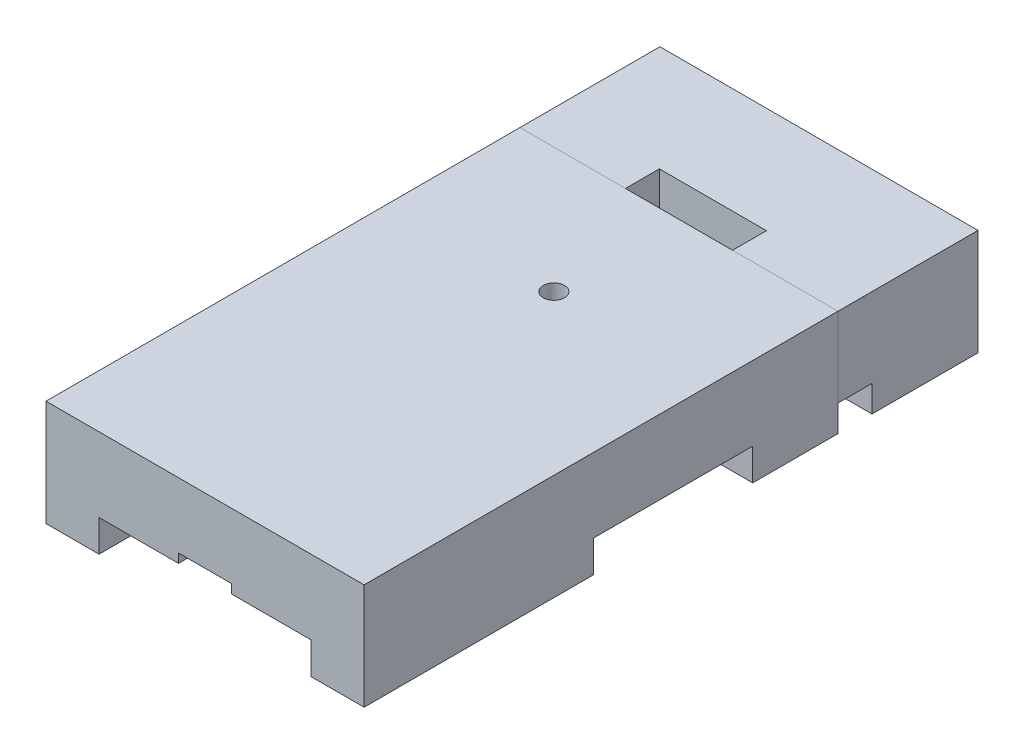
SolidWorks part; units mm, degrees
material "Nylon 6/10"
ref_plane "Front Plane" through (0, 0, 0) normal (0, 0, 1) x (1, 0, 0)
ref_plane "Top Plane" through (0, 0, 0) normal (0, 1, 0) x (1, 0, 0)
ref_plane "Right Plane" through (0, 0, 0) normal (1, 0, 0) x (0, 0, -1)
sketch "Sketch1" plane through (0, 0, 0) normal (0, 1, 0) x (1, 0, 0)
  line L1 (-38.1, -73.533) -> (38.1, -73.533)
  line L2 (-38.1, -73.533) -> (-38.1, 73.533)
  line L3 (-38.1, 73.533) -> (38.1, 73.533)
  line L4 (38.1, -73.533) -> (38.1, 73.533)
  line L5 (-38.1, -73.533) -> (38.1, 73.533) construction
  line L6 (-38.1, 73.533) -> (38.1, -73.533) construction
  point P0 (0, 0)
  dimension "D1" = 76.2
  dimension "D2" = 147.066
extrude "Boss-Extrude1" add sketch "Sketch1" along normal blind 12.7 and the other way blind 12.7
sketch "Sketch2" plane through (0, 0, -73.533) normal (0, 0, -1) x (-1, 0, 0)
  line L1 (-38.1, -12.7) -> (38.1, -12.7) construction
  circle A0 centre (0, -12.7) radius 4.7625
  dimension "D1" = 9.525
extrude "Cut-Extrude1" cut sketch "Sketch2" against normal blind 25.4
ref_plane "Plane1" through (0, -12.7, 0) normal (0, -1, 0) x (-1, 0, 0)
sketch "Sketch3" plane through (0, -12.7, 0) normal (0, -1, 0) x (-1, 0, 0)
  line L0 (10.922, 19.558) -> (44.45, 19.558)
  line L1 (-19.05, -83.058) -> (19.05, -83.058)
  line L2 (-25.4, -76.708) -> (-25.4, -18.542)
  line L3 (0, 0) -> (0, 102.0916) construction
  line L4 (25.4, -76.708) -> (25.4, -18.542)
  line L5 (-10.922, 19.558) -> (-10.922, 40.005)
  line L6 (25.4, -18.542) -> (44.45, -18.542)
  line L7 (-10.922, 40.005) -> (10.922, 40.005)
  line L8 (10.922, 19.558) -> (10.922, 40.005)
  line L10 (-44.45, -18.542) -> (-25.4, -18.542)
  line L11 (-44.45, -18.542) -> (-44.45, 19.558)
  line L12 (-44.45, 19.558) -> (-10.922, 19.558)
  line L13 (44.45, -18.542) -> (44.45, 19.558)
  line L14 (4.7625, 73.533) -> (4.7625, 48.133)
  line L15 (4.7625, 48.133) -> (-4.7625, 48.133)
  line L16 (-4.7625, 48.133) -> (-4.7625, 73.533)
  line L17 (-4.7625, 73.533) -> (-38.1, 73.533)
  line L18 (-38.1, 73.533) -> (-38.1, -73.533)
  line L19 (-38.1, -73.533) -> (38.1, -73.533)
  line L20 (38.1, -73.533) -> (38.1, 73.533)
  line L21 (38.1, 73.533) -> (4.7625, 73.533)
  line L25 (-4.7625, 73.533) -> (-38.1, 73.533) construction
  line L26 (-38.1, 73.533) -> (-38.1, -73.533) construction
  line L27 (-38.1, -73.533) -> (38.1, -73.533) construction
  line L28 (38.1, -73.533) -> (38.1, 73.533) construction
  line L29 (38.1, 73.533) -> (4.7625, 73.533) construction
  arc A0 (-25.4, -76.708) -> (-19.05, -83.058) centre (-19.05, -76.708) ccw
  arc A1 (19.05, -83.058) -> (25.4, -76.708) centre (19.05, -76.708) ccw
  dimension "D5" = 6.35
  dimension "D6" = 21.844
  dimension "D8" = 19.05
  dimension "D9" = 20.447
  dimension "D2" = 25.4
  dimension "D3" = 25.4
  dimension "D4" = 9.525
  dimension "D7" = 38.1
  dimension "D10" = 53.975
  dimension "D1" = 0
extrude "Cut-Extrude2" cut sketch "Sketch3" against normal blind 7.62
sketch "Sketch5" plane through (0, 0, 0) normal (0, 1, 0) x (1, 0, 0)
  line L0 (-4.7625, 73.533) -> (-38.1, 73.533) construction
  line L1 (12.827, 48.133) -> (-12.827, 48.133)
  line L2 (12.827, 40.005) -> (12.827, 48.133)
  line L3 (12.827, 40.005) -> (-12.827, 40.005)
  line L4 (0, 0) -> (0, 121.8983) construction
  line L6 (-12.827, 40.005) -> (-12.827, 48.133)
  point P17 (12.827, 40.005)
  point P20 (12.827, 48.133)
  dimension "D1" = 8.128
  dimension "D2" = 25.654
  dimension "D4" = 25.4
extrude "Cut-Extrude4" cut sketch "Sketch5" along normal through all and the other way through all
hole_wizard "1/4-20 Tapped Hole1" positions "Sketch8" profile "Sketch7" tap size "1/4-20" standard "ANSI Inch"
sketch "Sketch8" plane through (-11.0345, 12.7, 14.5475) normal (0, -1, 0) x (-1, 0, 0)
  line L1 (-23.8615, 62.6805) -> (1.7925, 62.6805) construction
  point P0 (-11.0345, 24.5805)
  dimension "D1" = 38.1
  dimension "D2" = 0
sketch "Sketch7" plane through (0, 12.7, -10.033) normal (1, 0, 0) x (0, 0, 1)
  line L0 (0, 0) -> (0, 20.5838)
  line L1 (0, 20.5838) -> (2.5527, 19.05)
  line L2 (2.5527, 19.05) -> (2.5527, 0)
  line L5 (2.5527, 0) -> (0, 0)
  line L10 (0, 20.5838) -> (-2.5527, 19.05) construction
  line L11 (0, -6.35) -> (0, 107.95) construction
  dimension "Tap Drill Dia." = 5.1054
  dimension "Tap Drill Depth" = 19.05
  dimension "Drill Angle" = 118
cosmetic thread "Hole Thread2" parameters "D1"=9.525, "D2"=6.35
sketch "Sketch9" plane through (0, -12.7, 0) normal (0, -1, 0) x (-1, 0, 0)
  line L0 (38.1, -28.067) -> (25.4, -28.067) construction
  line L1 (38.1, -18.542) -> (38.1, -73.533) construction
  line L2 (25.4, -73.533) -> (25.4, -18.542) construction
  line L3 (25.4, -18.542) -> (38.1, -18.542) construction
  line L4 (38.1, 29.083) -> (25.4, 29.083) construction
  line L5 (38.1, 73.533) -> (38.1, 19.558) construction
  line L6 (-10.922, 19.558) -> (-38.1, 19.558) construction
  line L7 (0, 0) -> (0, 53.9724) construction
  circle A0 centre (31.75, 29.083) radius 1.5964
  circle A1 centre (31.75, -28.067) radius 1.5964
  circle A2 centre (-31.75, -28.067) radius 1.5964
  circle A3 centre (-31.75, 29.083) radius 1.5964
  dimension "D1" = 9.525
  dimension "D2" = 3.1928
  dimension "D3" = 9.525
extrude "8-32 Tapped Hole" cut sketch "Sketch9" against normal blind 12.7
ref_plane "Plane2" through (0, 0, -19.558) normal (0, 0, 1) x (1, 0, 0)
ref_plane "Plane3" through (0, -5.08, 0) normal (0, -1, 0) x (-1, 0, 0)
sketch "Sketch11" plane through (0, -5.08, 0) normal (0, -1, 0) x (-1, 0, 0)
  line L1 (25.4, -73.533) -> (-25.4, -73.533) construction
  line L2 (0.0025, -32.893) -> (-0.0025, -32.893)
  line L3 (6.35, -39.2405) -> (6.35, -73.533)
  line L4 (6.35, -73.533) -> (-6.35, -73.533)
  line L5 (-6.35, -39.2405) -> (-6.35, -73.533)
  line L6 (6.35, -32.893) -> (-6.35, -73.533) construction
  line L7 (6.35, -73.533) -> (-6.35, -32.893) construction
  line L8 (0, -53.213) -> (0, -73.533) construction
  arc A0 (-0.0025, -32.893) -> (-6.35, -39.2405) centre (-0.0025, -39.2405) ccw
  arc A1 (0.0025, -32.893) -> (6.35, -39.2405) centre (0.0025, -39.2405) cw
  point P0 (0, -53.213)
  dimension "D2" = 6.3475
  dimension "D1" = 12.7
  dimension "D3" = 40.64
extrude "Cut-Extrude7" cut sketch "Sketch11" against normal blind 2.159
sketch "Sketch12" plane through (0, -5.08, 0) normal (0, -1, 0) x (1, 0, 0)
  line L0 (0, 0) -> (0, 79.2462) construction
  line L1 (-25.4, 73.533) -> (-6.35, 73.533) construction
  circle A0 centre (12.7, 54.483) radius 2.0193
  circle A1 centre (-12.7, 54.483) radius 2.0193
  dimension "D1" = 4.0386
  dimension "D2" = 25.4
  dimension "D3" = 19.05
extrude "Cut-Extrude8" cut sketch "Sketch12" against normal blind 12.7
sketch "Sketch13" plane through (0, -12.7, 0) normal (0, -1, 0) x (1, 0, 0)
  line L0 (38.1, -19.558) -> (38.1, -73.533) construction
  line L1 (12.827, -40.005) -> (38.1, -40.005)
  line L2 (12.827, -40.005) -> (12.827, -48.133)
  line L3 (12.827, -48.133) -> (38.1, -48.133)
  line L4 (38.1, -40.005) -> (38.1, -48.133)
  line L5 (12.827, -48.133) -> (4.7625, -48.133) construction
extrude "Cut-Extrude9" cut sketch "Sketch13" against normal blind 6.35
ref_plane "Plane4" through (0, 0, -40.005) normal (0, 0, -1) x (-1, 0, 0)
sketch "Sketch15" plane through (0, 0, -73.533) normal (0, 0, -1) x (-1, 0, 0)
  line L0 (-38.1, 0) -> (38.1, 0) construction
  line L1 (-38.1, -12.7) -> (-38.1, 12.7) construction
  line L2 (38.1, -12.7) -> (38.1, 12.7) construction
  circle A0 centre (-24.13, 0) radius 2.0193
  circle A1 centre (24.13, 0) radius 2.0193
  dimension "D1" = 4.0386
  dimension "D3" = 13.97
  dimension "D2" = 13.97
extrude "Cut-Extrude11" cut sketch "Sketch15" against normal blind 57.15
sketch "Sketch17" plane through (0, 0, -73.533) normal (0, 0, -1) x (-1, 0, 0)
  line L0 (-38.1, 0) -> (38.1, 0) construction
  line L3 (38.1, -12.7) -> (38.1, 12.7) construction
  circle A0 centre (-24.13, 0) radius 4.2164
  circle A1 centre (24.13, 0) radius 4.2164
  circle A3 centre (24.13, 0) radius 2.0193 construction
  circle A4 centre (-24.13, 0) radius 2.0193 construction
  dimension "D1" = 8.4328
extrude "Cut-Extrude12" cut sketch "Sketch17" against normal blind 5.461
sketch "Sketch19" plane through (0, -12.7, 0) normal (0, -1, 0) x (1, 0, 0)
  line L1 (-4.7625, -73.533) -> (-38.1, -73.533) construction
  line L2 (-38.1, -73.533) -> (-38.1, -19.558) construction
  circle A0 centre (-31.75, -57.658) radius 2.0193
  circle A1 centre (-12.7, -57.658) radius 2.0193
  dimension "D1" = 4.0386
  dimension "D2" = 15.875
  dimension "D3" = 6.35
  dimension "D4" = 19.05
extrude "Cut-Extrude14" cut sketch "Sketch19" against normal blind 12.7
sketch "Sketch22" plane through (0, -12.7, 0) normal (0, -1, 0) x (1, 0, 0)
  line L0 (-12.7, -35.1155) -> (12.7, -35.1155) construction
  line L1 (-12.7, -24.4475) -> (12.7, -24.4475) construction
  line L2 (-12.7, -35.9092) -> (12.7, -35.9092)
  line L3 (-12.7, -34.3217) -> (12.7, -34.3217)
  line L4 (-12.7, -23.6537) -> (12.7, -23.6537)
  line L5 (-12.7, -25.2412) -> (12.7, -25.2412)
  line L6 (0, -39.4682) -> (0, -19.7785) construction
  line L7 (10.922, -29.7815) -> (-10.922, -29.7815) construction
  line L10 (10.922, -40.005) -> (10.922, -19.558) construction
  line L11 (-10.922, -19.558) -> (-10.922, -40.005) construction
  arc A0 (-12.7, -23.6537) -> (-12.7, -25.2412) centre (-12.7, -24.4475) ccw
  arc A1 (12.7, -25.2412) -> (12.7, -23.6537) centre (12.7, -24.4475) ccw
  arc A2 (-12.7, -35.9092) -> (-12.7, -34.3217) centre (-12.7, -35.1155) cw
  arc A3 (12.7, -34.3217) -> (12.7, -35.9092) centre (12.7, -35.1155) cw
  point P6 (0, -24.4475)
  point P17 (0, -35.1155)
  dimension "D1" = 1.5875
  dimension "D2" = 25.4
  dimension "D3" = 10.668
extrude "Cut-Extrude16" cut sketch "Sketch22" against normal blind 2.286
sketch "Sketch23" plane through (0, -12.7, 0) normal (0, -1, 0) x (1, 0, 0)
  line L1 (-10.922, -40.005) -> (10.922, -40.005)
  line L2 (-10.922, -40.005) -> (-10.922, -22.733)
  line L3 (-7.747, -19.558) -> (7.747, -19.558)
  line L4 (10.922, -40.005) -> (10.922, -22.733)
  arc A0 (-7.747, -19.558) -> (-10.922, -22.733) centre (-7.747, -22.733) ccw
  arc A1 (7.747, -19.558) -> (10.922, -22.733) centre (7.747, -22.733) cw
  point P9 (10.922, -19.558)
  dimension "D1" = 3.175
extrude "Cut-Extrude18" cut sketch "Sketch23" against normal blind 11.176
split "Split1" trim tools "Plane4" bodies to split 123 resulting bodies 124 125
